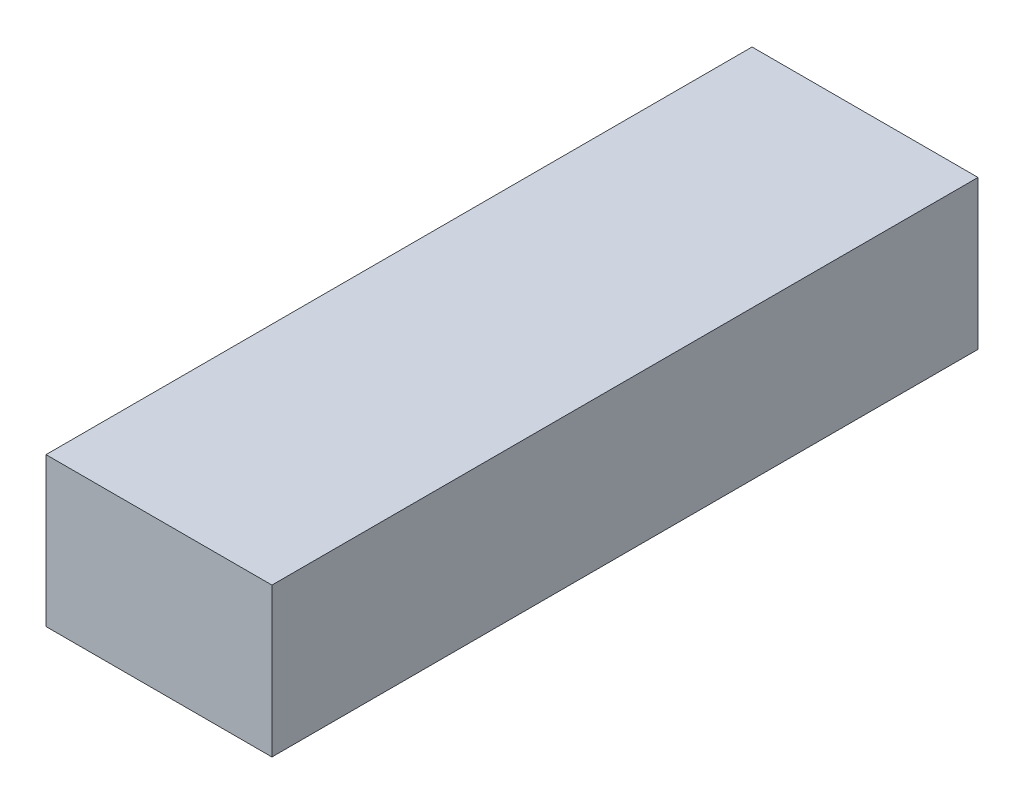
SolidWorks part; units mm, degrees
ref_plane "Front Plane" through (0, 0, 0) normal (0, 0, 1) x (1, 0, 0)
ref_plane "Top Plane" through (0, 0, 0) normal (0, 1, 0) x (1, 0, 0)
ref_plane "Right Plane" through (0, 0, 0) normal (1, 0, 0) x (0, 0, -1)
sketch "Sketch1" plane through (0, 0, 0) normal (0, 1, 0) x (1, 0, 0)
  line L1 (0, 0) -> (44, 0)
  line L2 (0, 0) -> (0, 137.5)
  line L3 (0, 137.5) -> (44, 137.5)
  line L4 (44, 0) -> (44, 137.5)
  dimension "D1" = 137.5
  dimension "D2" = 44
extrude "Boss-Extrude1" add sketch "Sketch1" along normal blind 29
